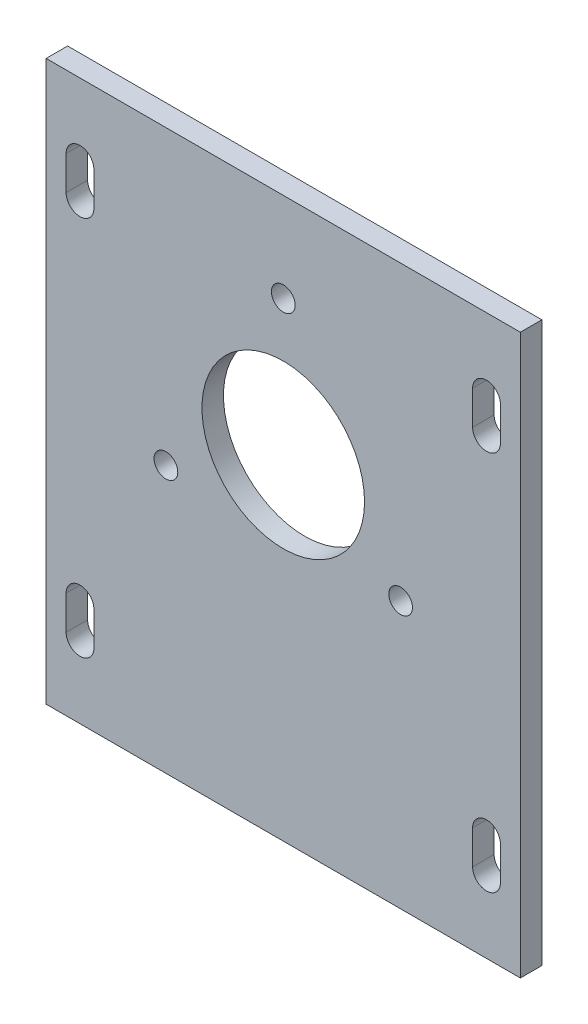
SolidWorks part; units mm, degrees
ref_plane "Front Plane" through (0, 0, 0) normal (0, 0, 1) x (1, 0, 0)
ref_plane "Top Plane" through (0, 0, 0) normal (0, 1, 0) x (1, 0, 0)
ref_plane "Right Plane" through (0, 0, 0) normal (1, 0, 0) x (0, 0, -1)
sketch "Sketch1" plane through (0, 0, 0) normal (0, 0, 1) x (1, 0, 0)
  line L0 (0, 38.1) -> (0, -38.1) construction
  line L1 (-35, -38.1) -> (35, -38.1)
  line L2 (-35, -38.1) -> (-35, 38.1)
  line L3 (-35, 38.1) -> (35, 38.1)
  line L4 (35, -38.1) -> (35, 38.1)
  line L5 (-35, -38.1) -> (35, 38.1) construction
  line L6 (-35, 38.1) -> (35, -38.1) construction
  line L7 (-35, 0) -> (35, 0) construction
  line L8 (-35, 28.1) -> (0, 28.1) construction
  line L9 (-30, 25.6) -> (-30, 30.6) construction
  line L10 (-32.05, 25.6) -> (-32.05, 30.6)
  line L11 (-27.95, 25.6) -> (-27.95, 30.6)
  line L12 (30, 25.6) -> (30, 30.6) construction
  line L13 (32.05, 25.6) -> (32.05, 30.6)
  line L14 (27.95, 25.6) -> (27.95, 30.6)
  line L15 (-30, -25.6) -> (-30, -30.6) construction
  line L16 (-32.05, -25.6) -> (-32.05, -30.6)
  line L17 (-27.95, -25.6) -> (-27.95, -30.6)
  line L18 (30, -25.6) -> (30, -30.6) construction
  line L19 (32.05, -25.6) -> (32.05, -30.6)
  line L20 (27.95, -25.6) -> (27.95, -30.6)
  circle A0 centre (-30, 28.1) radius 2.05 construction
  arc A1 (-32.05, 25.6) -> (-27.95, 25.6) centre (-30, 25.6) ccw
  arc A2 (-27.95, 30.6) -> (-32.05, 30.6) centre (-30, 30.6) ccw
  arc A3 (32.05, 25.6) -> (27.95, 25.6) centre (30, 25.6) cw
  arc A4 (27.95, 30.6) -> (32.05, 30.6) centre (30, 30.6) cw
  arc A5 (-32.05, -25.6) -> (-27.95, -25.6) centre (-30, -25.6) cw
  arc A6 (-27.95, -30.6) -> (-32.05, -30.6) centre (-30, -30.6) cw
  arc A7 (32.05, -25.6) -> (27.95, -25.6) centre (30, -25.6) ccw
  arc A8 (27.95, -30.6) -> (32.05, -30.6) centre (30, -30.6) ccw
  circle A10 centre (0, 8.1) radius 20 construction
  circle A11 centre (0, 28.1) radius 1.75
  circle A12 centre (17.3205, -1.9) radius 1.75
  circle A13 centre (-17.3205, -1.9) radius 1.75
  circle A14 centre (0, 8.1) radius 12
  circle A15 centre (0, 8.1) radius 33.35 construction
  point P0 (0, 0)
  point P16 (-30, 28.1)
  point P24 (30, 28.1)
  point P31 (-30, -28.1)
  point P38 (30, -28.1)
  point P52 (0, 8.1)
  dimension "D4" = 4.1
  dimension "D6" = 2.05
  dimension "D7" = 40
  dimension "D9" = 3.5
  dimension "D11" = 24
  dimension "D12" = 66.7
  dimension "D1" = 76.2
  dimension "D2" = 70
  dimension "D3" = 10
  dimension "D5" = 5
  dimension "D8" = 46.2
  dimension "D13" = 5
  dimension "D10" = 3
extrude "Boss-Extrude1" add sketch "Sketch1" along normal blind 3.175
sketch "Sketch3" plane through (0, 0, 3.175) normal (0, 0, 1) x (1, 0, 0)
  line L0 (0, 0) -> (62.8834, 0) construction
  line L1 (-35, 38.1) -> (35, 38.1)
  line L2 (-35, 38.1) -> (-35, 41.275)
  line L3 (-35, 41.275) -> (35, 41.275)
  line L4 (35, 38.1) -> (35, 41.275)
  line L5 (-35, -41.275) -> (35, -41.275)
  line L6 (35, -38.1) -> (35, -41.275)
  line L7 (-35, -38.1) -> (35, -38.1)
  line L8 (-35, -38.1) -> (-35, -41.275)
  dimension "D1" = 3.175
extrude "Boss-Extrude2" add sketch "Sketch3" against normal up to surface (3.175 mm away) up to face at (19.0705, -1.9, 0)
